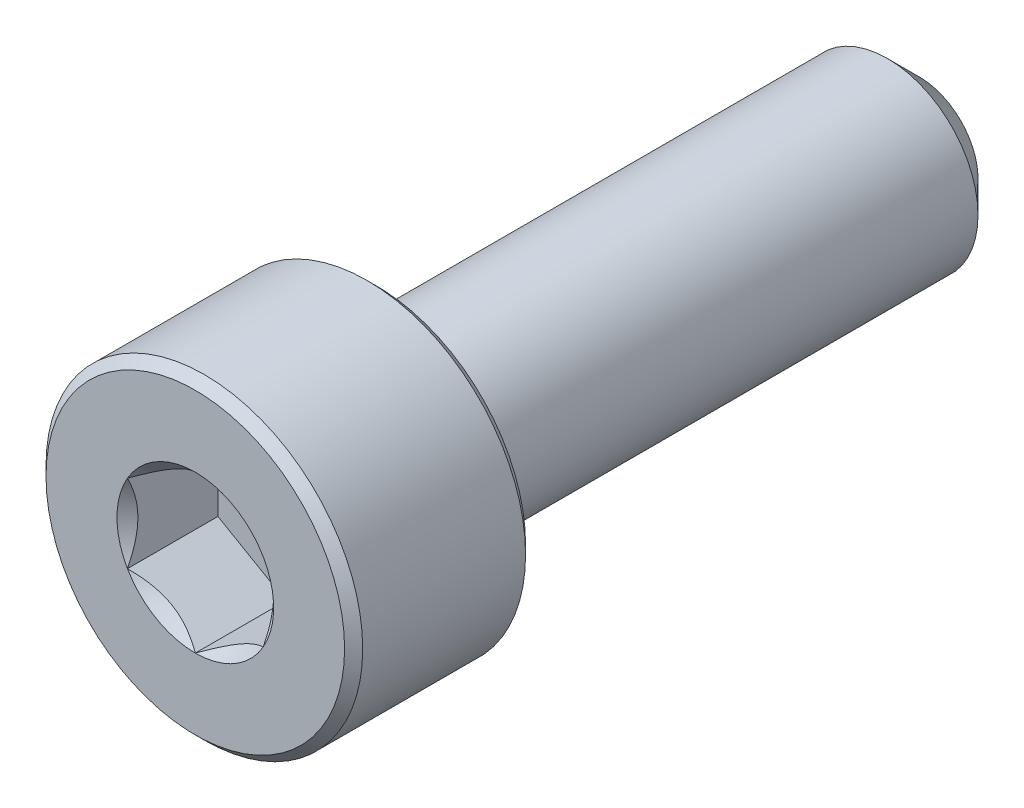
SolidWorks part; units mm, degrees
material "Alloy Steel"
ref_plane "Front Plane" through (0, 0, 0) normal (0, 0, 1) x (1, 0, 0)
ref_plane "Top Plane" through (0, 0, 0) normal (0, 1, 0) x (1, 0, 0)
ref_plane "Right Plane" through (0, 0, 0) normal (1, 0, 0) x (0, 0, -1)
sketch "Sketch1" plane through (0, 0, 0) normal (1, 0, 0) x (0, 0, -1)
  line L0 (-8, 0) -> (8, 0) construction
  line L1 (8, 0) -> (8, 1.3) construction
  line L2 (8, 1.3) -> (7.3, 2) construction
  line L3 (7.3, 2) -> (-4, 2) construction
  line L5 (-4, 2) -> (-4, 3.5) construction
  line L6 (-4, 3.5) -> (-8, 3.5) construction
  line L7 (-8, 3.5) -> (-8, 0) construction
  line L8 (8, 1.3) -> (8, 2) construction
  line L9 (7.9563, 2.0758) -> (8.3063, 1.4696) construction
  line L10 (8.3063, 1.4696) -> (8.6562, 2.0758) construction
  line L11 (8.6562, 2.0758) -> (7.9563, 2.0758) construction
  line L12 (8.3063, 2.0758) -> (8.3063, 2) construction
  line L13 (8.3063, 1.4696) -> (8.3063, 1.5453) construction
  line L14 (8.2625, 1.5453) -> (8.35, 1.5453) construction
  line L15 (8, 2) -> (8.6125, 2) construction
  line L16 (7.9781, 2.0379) -> (8.6344, 2.0379) construction
  line L17 (8, 0) -> (8, -2) construction
  line L18 (-4.2, 3.5) -> (-4, 3.3) construction
  line L19 (-7.8, 3.5) -> (-8, 3.3) construction
  point P0 (-8, 1.5)
  point P3 (5.55, 2)
  point P4 (0, 0)
  point P22 (8.3063, 1.5453)
  point P24 (-4, 2)
  point P25 (8.3063, 2)
  point P28 (8.3063, 2.0379)
  point P29 (5.55, -2)
  point P31 (-6, 3.5)
  point P37 (-4.7, 3.5)
  point P38 (-7.7, 3.5)
  point P41 (-6, 0)
  dimension "head height" = 4
  dimension "D1" = 45
  dimension "Head Diameter" = 7
  dimension "Thread Size" = 4
  dimension "drive size" = 3
  dimension "Thread Pitch" = 0.7
  dimension "D2" = 0.0875
  dimension "D3" = 0.7
  dimension "D4" = 2.45
  dimension "D7" = 0.2
  dimension "D8" = 0.2
  dimension "D9" = 0.2
  dimension "D10" = 0.1
  dimension "D11" = 0.5
  dimension "length" = 12
  dimension "Drive Depth" = 2
sketch "Sketch2" plane through (0, 0, 0) normal (1, 0, 0) x (0, 0, -1)
  line L1 (-7.8, 3.5) -> (-4.2, 3.5)
  line L4 (7.3, 2) -> (8, 1.3)
  line L5 (8, 1.3) -> (8, 0)
  line L6 (-4.2, 3.5) -> (-4, 3.3) construction
  line L7 (8, 0) -> (-8, 0)
  line L8 (-7.8, 3.5) -> (-8, 3.3) construction
  line L9 (-4.2, 3.5) -> (-4, 3.3)
  line L10 (-7.8, 3.5) -> (-8, 3.3)
  line L11 (-8, 3.3) -> (-8, 0)
  line L12 (-4, 3.3) -> (-4, 2)
  line L13 (-4, 2) -> (7.3, 2)
revolve "Revolve1" add sketch "Sketch2" angle 360 about L7
sketch "Sketch3" plane through (0, 0, 8) normal (0, 0, 1) x (1, 0, 0)
  line L1 (0, 1.7321) -> (-1.5, 0.866)
  line L2 (-1.5, 0.866) -> (-1.5, -0.866)
  line L3 (-1.5, -0.866) -> (0, -1.7321)
  line L4 (0, -1.7321) -> (1.5, -0.866)
  line L5 (1.5, -0.866) -> (1.5, 0.866)
  line L6 (1.5, 0.866) -> (0, 1.7321)
  circle A0 centre (0, 0) radius 1.5 construction
  dimension "D1" = 3
extrude "Cut-Extrude1" cut sketch "Sketch3" against normal up to vertex (2 mm away) up to point (0, 0, 6)
sketch "Sketch4" plane through (0, 0, 8) normal (0, 0, 1) x (1, 0, 0)
  circle A0 centre (0, 0) radius 1.7321
extrude "Cut-Extrude2" cut sketch "Sketch4" against normal blind 0.5 draft 45
ref_plane "Plane1" [suppressed] through (0, 0, 4) normal (0, 0, 1) x (1, 0, 0)
split "Split1" [suppressed] bodies to split 106
sketch "Sketch6" [suppressed] plane through (0, 0, -8) normal (0, 0, -1) x (-1, 0, 0)
  circle A0 centre (0, 0) radius 2
curve "Helix/Spiral1" [suppressed] pitch 0.7 height 12.7 turns 18.1429
sketch "Sketch7" [suppressed] plane through (0, 0, 0) normal (1, 0, 0) x (0, 0, -1)
  line L0 (7.9781, 2.0379) -> (8.6344, 2.0379)
  line L1 (8.6344, 2.0379) -> (8.35, 1.5453)
  line L2 (8.35, 1.5453) -> (8.2625, 1.5453)
  line L3 (8.2625, 1.5453) -> (7.9781, 2.0379)
sweep "Cut-Sweep1" [suppressed] cut profiles "Sketch7" path "Helix/Spiral1"
sketch "Sketch8" [suppressed] plane through (0, 0, 4) normal (0, 0, -1) x (-1, 0, 0)
  circle A0 centre (0, 0) radius 2
extrude "Boss-Extrude1" [suppressed] add sketch "Sketch8" along normal through all draft 45
ref_plane "Plane2" [suppressed] through (0, 0, 6) normal (0, 0, 1) x (1, 0, 0)
sketch "Sketch9" [suppressed] plane through (0, 0, 6) normal (0, 0, 1) x (1, 0, 0)
  line L0 (0, 3.4038) -> (0.0916, 3.4988)
  line L1 (0, 3.4038) -> (-0.0916, 3.4988)
  line L2 (0, 3.5) -> (0, 0) construction
  line L3 (-0.0916, 3.4988) -> (0, 0) construction
  line L4 (0, 0) -> (0.0916, 3.4988) construction
  arc A0 (0.0916, 3.4988) -> (-0.0916, 3.4988) centre (0, 0) ccw
  circle A1 centre (0, 0) radius 3.4038 construction
  dimension "D1" = 7
  dimension "D2" = 6.8075
  dimension "D3" = 3
extrude "Cut-Extrude4" [suppressed] cut sketch "Sketch9" against normal up to vertex and the other way up to vertex
pattern_circular "CirPattern2" [suppressed] count 96 over 360 about axis through (0, 0, 8) along (0, 0, -1) of bodies 113
equation "\"D2@Sketch1\" = \"Thread Pitch@Sketch1\" / 8"
equation "\"D3@Sketch1\" = \"Thread Pitch@Sketch1\""
equation "\"D3@Helix/Spiral1\" = \"length@Sketch1\" + \"Thread Pitch@Sketch1\""
equation "\"D4@Helix/Spiral1\" = \"Thread Pitch@Sketch1\""
equation "\"D4@Sketch1\" = \"Thread Pitch@Sketch1\" * 3.5"
equation "\"D7@Sketch1\"=\"head height@Sketch1\"*.05"
equation "\"D8@Sketch1\"=\"D7@Sketch1\""
equation "\"D9@Sketch1\"=\"D7@Sketch1\""
equation "\"D10@Sketch1\"=\"D7@Sketch1\"/2"
equation "\"D11@Sketch1\"=\"D10@Sketch1\"*5"
equation "\"D1@CirPattern2\"=( 360 / \"D3@Sketch9\" )*0.8"
equation "\"D1@Sketch3\" = \"drive size@Sketch1\""
equation "\"D2@Sketch9\"=\"Head Diameter@Sketch1\" * 0.9725"
